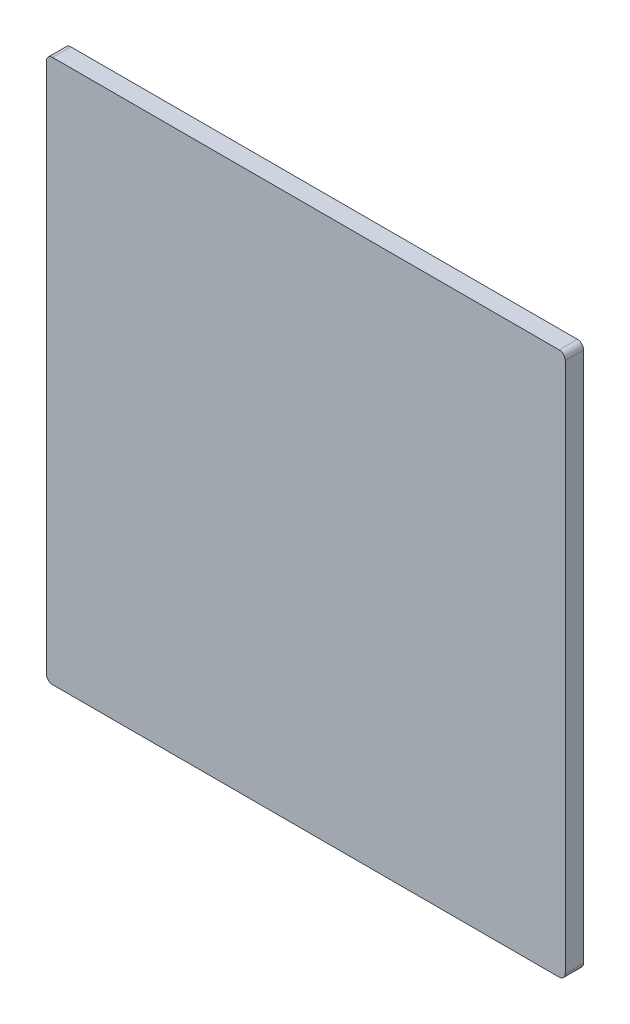
SolidWorks part; units mm, degrees
ref_plane "Front Plane" through (0, 0, 0) normal (1, 0, 0) x (0, 1, 0)
ref_plane "Top Plane" through (0, 0, 0) normal (0, 0, 1) x (0, 1, 0)
ref_plane "Right Plane" through (0, 0, 0) normal (0, 1, 0) x (-1, 0, 0)
sketch "Sketch1" plane through (0, 0, 0) normal (0, 0, 1) x (0, 1, 0)
  line L1 (445, -425) -> (-445, -425)
  line L2 (445, -425) -> (445, 425)
  line L3 (445, 425) -> (-445, 425)
  line L4 (-445, -425) -> (-445, 425)
  line L5 (445, -425) -> (-445, 425) construction
  line L6 (445, 425) -> (-445, -425) construction
  point P0 (0, 0)
  dimension "D1" = 890
  dimension "D2" = 850
extrude "Boss-Extrude1" add sketch "Sketch1" along normal blind 30
fillet "Fillet1" radius 10 4 edges at (-425, -445, 15) (-425, 445, 15) (425, 445, 15) (425, -445, 15)
